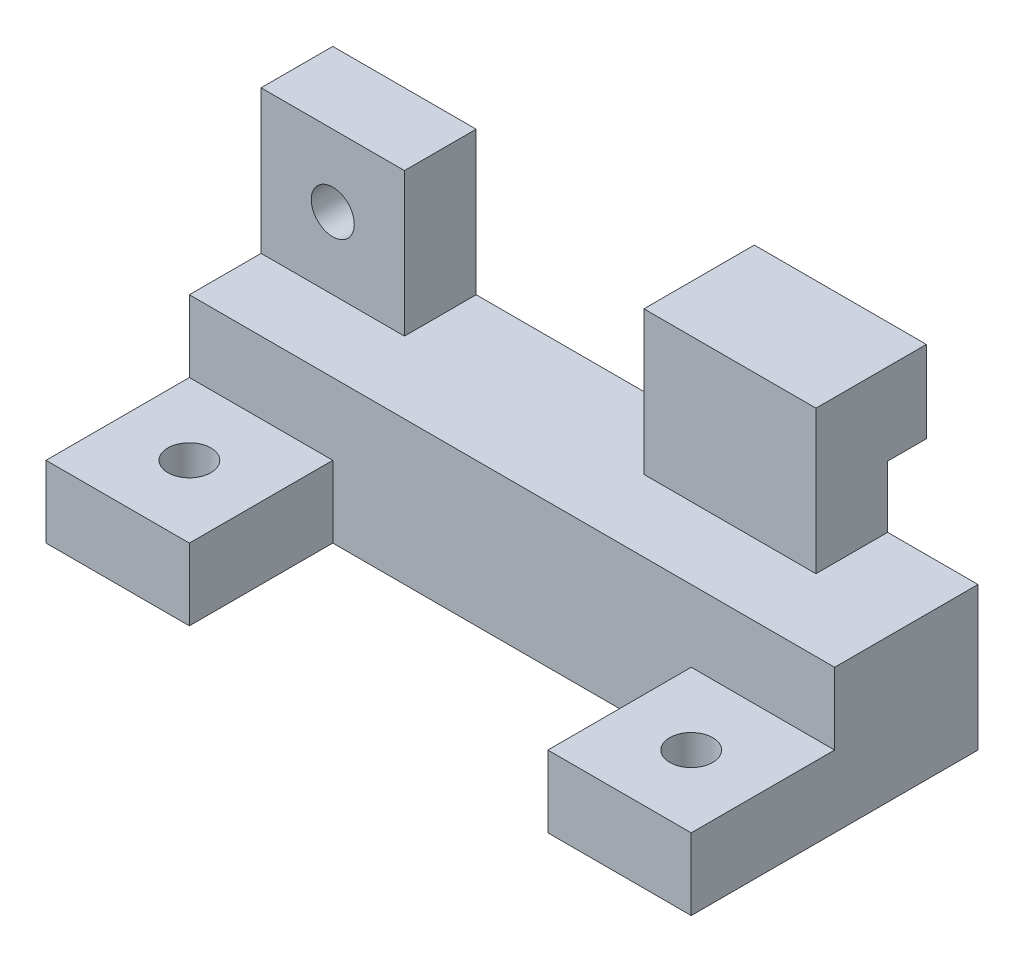
SolidWorks part; units mm, degrees
ref_plane "Front Plane" through (0, 0, 0) normal (0, 0, 1) x (1, 0, 0)
ref_plane "Top Plane" through (0, 0, 0) normal (0, 1, 0) x (1, 0, 0)
ref_plane "Right Plane" through (0, 0, 0) normal (1, 0, 0) x (0, 0, -1)
sketch "Sketch1" plane through (0, 0, 0) normal (0, 0, 1) x (1, 0, 0)
  line L1 (0, 0) -> (45, 0)
  line L2 (0, 0) -> (0, 10)
  line L3 (0, 10) -> (45, 10)
  line L4 (45, 0) -> (45, 10)
  dimension "D1" = 45
  dimension "D2" = 10
extrude "Boss-Extrude1" add sketch "Sketch1" along normal blind 10
sketch "Sketch2" plane through (0, 10, 0) normal (0, 1, 0) x (1, 0, 0)
  line L0 (45, 0) -> (0, 0) construction
  line L1 (45, 0) -> (35, 0)
  line L2 (45, 0) -> (45, -5)
  line L3 (45, -5) -> (35, -5)
  line L4 (35, 0) -> (35, -5)
  line L5 (6.3, 0) -> (18.3, 0)
  line L6 (6.3, 0) -> (6.3, -5)
  line L7 (6.3, -5) -> (18.3, -5)
  line L8 (18.3, 0) -> (18.3, -5)
  line L9 (0, -10) -> (0, 0) construction
  dimension "D1" = 5
  dimension "D2" = 10
  dimension "D3" = 5
  dimension "D4" = 6.3
  dimension "D5" = 12
extrude "Boss-Extrude2" add sketch "Sketch2" along normal blind 10
sketch "Sketch3" plane through (0, 0, 10) normal (0, 0, 1) x (1, 0, 0)
  line L1 (0, 0) -> (10, 0)
  line L2 (0, 0) -> (0, 5)
  line L3 (0, 5) -> (10, 5)
  line L4 (10, 0) -> (10, 5)
  line L5 (45, 0) -> (35, 0)
  line L6 (45, 0) -> (45, 5)
  line L7 (45, 5) -> (35, 5)
  line L8 (35, 0) -> (35, 5)
  dimension "D1" = 10
  dimension "D2" = 10
  dimension "D3" = 5
  dimension "D4" = 5
extrude "Boss-Extrude3" add sketch "Sketch3" along normal blind 10
sketch "Sketch4" plane through (0, 0, 0) normal (-1, 0, 0) x (0, 0, 1)
  line L0 (0, 10) -> (0, 0) construction
  line L1 (20, 0) -> (0, 0) construction
  circle A0 centre (5, 5) radius 1.5
  dimension "D3" = 3
  dimension "D1" = 5
  dimension "D2" = 5
extrude "Cut-Extrude1" cut sketch "Sketch4" against normal blind 5
sketch "Sketch7" plane through (45, 0, 0) normal (1, 0, 0) x (0, 0, -1)
  line L3 (-10, 10) -> (0, 10)
  line L4 (-10, 10) -> (-10, 0)
  line L5 (-10, 0) -> (0, 0)
  line L6 (0, 10) -> (0, 0)
sketch "Sketch9" plane through (0, 5, 0) normal (0, 1, 0) x (1, 0, 0)
  line L0 (45, -20) -> (45, -10) construction
  line L1 (45, -20) -> (35, -20) construction
  circle A0 centre (40, -15) radius 1.5
  dimension "D3" = 3
  dimension "D1" = 5
  dimension "D2" = 5
extrude "Cut-Extrude6" cut sketch "Sketch9" against normal blind 5
sketch "Sketch10" plane through (0, 0, 5) normal (0, 0, 1) x (1, 0, 0)
  line L0 (35, 20) -> (35, 10) construction
  line L3 (35, 10) -> (45, 10) construction
  circle A0 centre (40, 15) radius 1.5
  dimension "D3" = 3
  dimension "D1" = 5
  dimension "D2" = 5
extrude "Cut-Extrude7" cut sketch "Sketch10" against normal blind 5
sketch "Sketch11" plane through (0, 0, 0) normal (0, 0, -1) x (-1, 0, 0)
  line L0 (-18.3, 20) -> (-18.3, 10) construction
  line L1 (-6.3, 20) -> (-18.3, 20)
  line L2 (-6.3, 20) -> (-6.3, 14.3)
  line L3 (-6.3, 14.3) -> (-18.3, 14.3)
  line L4 (-18.3, 20) -> (-18.3, 14.3)
  line L5 (-18.3, 14.3) -> (-6.3, 14.3) construction
extrude "Boss-Extrude4" add sketch "Sketch11" along normal blind 2.7
extrude "Boss-Extrude5" add sketch "Sketch7" along normal blind 35
sketch "Sketch13" plane through (0, 10, 0) normal (0, 1, 0) x (1, 0, 0)
  line L0 (80, 0) -> (45, 0) construction
  line L1 (61.7, 0) -> (73.7, 0)
  line L2 (61.7, 0) -> (61.7, -5)
  line L3 (61.7, -5) -> (73.7, -5)
  line L4 (73.7, 0) -> (73.7, -5)
  line L5 (80, 0) -> (80, -10) construction
  dimension "D1" = 6.3
  dimension "D2" = 5
  dimension "D3" = 12
extrude "Boss-Extrude6" add sketch "Sketch13" along normal blind 10
sketch "Sketch14" plane through (0, 0, 0) normal (0, 0, -1) x (-1, 0, 0)
  line L0 (-61.7, 20) -> (-61.7, 10) construction
  line L1 (-73.7, 20) -> (-61.7, 20)
  line L2 (-73.7, 20) -> (-73.7, 14.3)
  line L3 (-73.7, 14.3) -> (-61.7, 14.3)
  line L4 (-61.7, 20) -> (-61.7, 14.3)
  dimension "D1" = 5.7
extrude "Boss-Extrude7" add sketch "Sketch14" along normal blind 2.7
sketch "Sketch15" plane through (35, 0, 0) normal (-1, 0, 0) x (0, 0, 1)
  line L1 (0, 20) -> (20, 20)
  line L2 (0, 20) -> (0, 0)
  line L3 (0, 0) -> (20, 0)
  line L4 (20, 20) -> (20, 0)
  line L5 (0, 20) -> (-5, 20)
  line L6 (0, 20) -> (0, 0)
  line L7 (0, 0) -> (-5, 0)
  line L8 (-5, 20) -> (-5, 0)
  line M1 (0, 10) -> (5, 10)
  line M2 (5, 10) -> (5, 20)
  line M3 (5, 20) -> (0, 20)
  line M4 (0, 20) -> (0, 10)
  dimension "D1" = 5
extrude "Cut-Extrude9" cut sketch "Sketch15" along normal blind 50 contours L4 L1 L2 L3 M2 M1 | M4 M1 M2 M3 | L5 L8 L7 L2 M4 region at (35, 15, 2.5) region at (35, 10, -2.5) region at (35, 9.2857, 11.0714)
sketch "Sketch16" plane through (0, 0, 10) normal (0, 0, 1) x (1, 0, 0)
  line L1 (80, 0) -> (70, 0)
  line L2 (80, 0) -> (80, 5)
  line L3 (80, 5) -> (70, 5)
  line L4 (70, 0) -> (70, 5)
  dimension "D1" = 5
  dimension "D2" = 10
extrude "Boss-Extrude8" add sketch "Sketch16" along normal blind 10
sketch "Sketch17" plane through (0, 5, 0) normal (0, 1, 0) x (1, 0, 0)
  line L0 (80, -20) -> (80, -10) construction
  line L1 (80, -20) -> (70, -20) construction
  circle A0 centre (75, -15) radius 1.5
  dimension "D3" = 3
  dimension "D1" = 5
  dimension "D2" = 5
extrude "Cut-Extrude10" cut sketch "Sketch17" against normal blind 5
